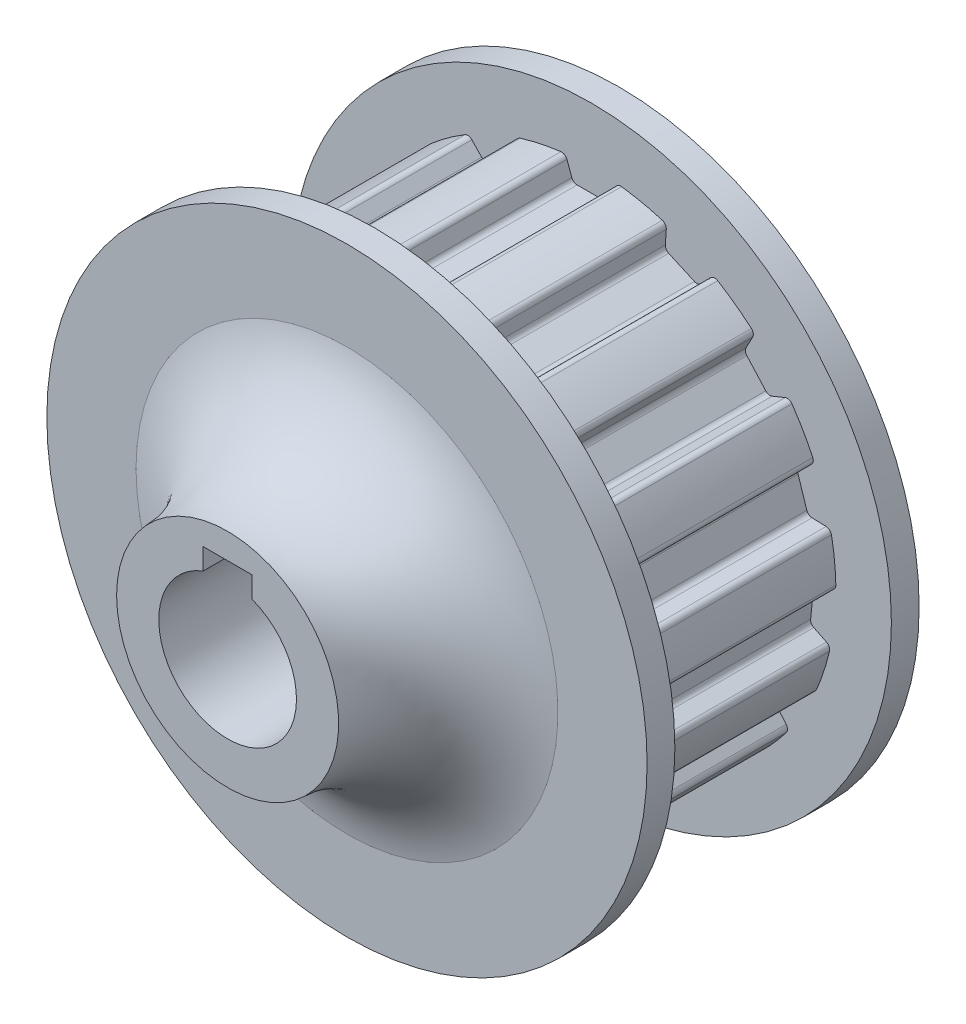
SolidWorks part; units mm, degrees
ref_plane "Front Plane" through (0, 0, 0) normal (0, 0, 1) x (1, 0, 0)
ref_plane "Top Plane" through (0, 0, 0) normal (0, 1, 0) x (1, 0, 0)
ref_plane "Right Plane" through (0, 0, 0) normal (1, 0, 0) x (0, 0, -1)
sketch "Sketch1" plane through (0, 0, 0) normal (0, 1, 0) x (1, 0, 0)
  line L0 (0, 36.1296) -> (0, -19.4741) construction
sketch "Sketch7" plane through (0, 0, 0) normal (0, 0, 1) x (1, 0, 0)
  line L0 (0, 0) -> (0, 20.9536) construction
  line L1 (-2.325, 21.9086) -> (-2.9401, 23.5986) construction
  line L2 (-2.325, 21.9086) -> (-1.6298, 19.9986) construction
  line L3 (-1.6298, 19.9986) -> (1.6298, 19.9986) construction
  line L4 (1.6298, 19.9986) -> (2.325, 21.9086) construction
  line L5 (2.325, 21.9086) -> (-2.325, 21.9086) construction
  line L6 (0, 19.9986) -> (0, 21.9086) construction
  line L7 (2.325, 21.9086) -> (2.9401, 23.5986) construction
  line L8 (-2.9401, 23.5986) -> (2.9401, 23.5986) construction
  line L9 (0, 0) -> (8.5226, 19.1421) construction
  line L10 (8.5226, 19.1421) -> (8.9611, 20.1269) construction
  line L11 (0, 21.9086) -> (0, 22.0316) construction
  line L12 (0, 22.0316) -> (0, 23.7811) construction
  line L13 (0, 22.9064) -> (9.3169, 20.926) construction
  line L14 (8.9611, 20.1269) -> (9.6726, 21.7251) construction
  circle A1 centre (0, 0) radius 20.9536 construction
  circle A2 centre (-1.2727, 20.5086) radius 0.51 construction
  circle A3 centre (1.2727, 20.5086) radius 0.51 construction
  circle A4 centre (0, 0) radius 22.0316
  circle A5 centre (0, 0) radius 23.7811 construction
  dimension "D3" = 40
  dimension "D6" = 1.02
  dimension "D1" = 3.6
  dimension "D2" = 24
  dimension "D7" = 9.525
  dimension "D4" = 1.91
  dimension "D5" = 4.65
extrude "Boss-Extrude1" add sketch "Sketch7" along normal blind 7.25 and the other way blind 7.25 contours A4 region at (0, 0, 0)
sketch "Sketch14" plane through (0, 0, 0) normal (1, 0, 0) x (0, 0, -1)
  line L0 (-18, 0) -> (-18, 10)
  line L1 (-18, 0) -> (0, 0)
  line L2 (0, 0) -> (0, 19)
  line L3 (0, 19) -> (-7.25, 19)
  line L4 (-7.25, 19) -> (-18, 10)
  line L5 (-7.25, 22.0316) -> (-7.25, -22.0316) construction
  line L6 (-18, 6.7395) -> (-3.3555, 19) construction
  arc A0 (-7.25, 19) -> (-18, 10) centre (-18.1316, 21.0773) cw
  dimension "D1" = 10
  dimension "D2" = 19
  dimension "D3" = 18
  dimension "D4" = 2.5
revolve "Revolve1" add sketch "Sketch14" angle 360 about L0 region at (0, 7.5733, 7.5341) region at (0, 9.2725, 16.1663) region at (0, 17.2765, 6.6188)
sketch "Sketch9" plane through (0, 0, 0) normal (0, 0, 1) x (1, 0, 0)
  line L0 (2, 0) -> (-2, 0) construction
  line L1 (-2, 0) -> (-2, 7.5) construction
  line L2 (-2, 7.5) -> (2, 7.5) construction
  line L3 (2, 7.5) -> (2, 0) construction
  circle A0 centre (0, 0) radius 6 construction
  dimension "D1" = 12
  dimension "D2" = 4
  dimension "D3" = 7.5
sketch "Sketch10" plane through (0, 0, 0) normal (0, 0, 1) x (1, 0, 0)
  line L0 (2, 0) -> (-2, 0) construction
  line L1 (-2.2, 7.7) -> (2.2, 7.7)
  line L2 (-2.2, 7.7) -> (-2.2, 0)
  line L3 (-2.2, 0) -> (2.2, 0)
  line L4 (2.2, 7.7) -> (2.2, 0)
  line L5 (-2, 7.5) -> (2, 7.5) construction
  line L6 (2, 7.5) -> (2, 0) construction
  circle A0 centre (0, 0) radius 6.2
  circle A1 centre (0, 0) radius 6 construction
  dimension "D1" = 0.2
  dimension "D2" = 0.2
  dimension "D3" = 0.2
extrude "Cut-Extrude3" cut sketch "Sketch10" against normal through all both and the other way through all contours A0 L4 L1 L2 | L2 A0 L4 L3 | L4 A0 L2 L3 region at (0, 6.8793, 0) region at (0, 3.0348, 0) region at (0, -0.8613, 0)
sketch "Sketch11" plane through (0, 0, 0) normal (0, 1, 0) x (1, 0, 0)
  line L0 (22.0316, 7.25) -> (-22.0316, 7.25) construction
  line L1 (11, 7.25) -> (17.5, 7.25)
  line L2 (11, 7.25) -> (11, 4.75)
  line L3 (11, 4.75) -> (17.5, 4.75)
  line L4 (17.5, 7.25) -> (17.5, 4.75)
  line L5 (-22.0316, -7.25) -> (22.0316, -7.25) construction
  line L6 (11, -7.25) -> (17.5, -7.25)
  line L7 (11, -7.25) -> (11, -4.75)
  line L8 (11, -4.75) -> (17.5, -4.75)
  line L9 (17.5, -7.25) -> (17.5, -4.75)
  line L11 (11, 4.75) -> (11, -4.75) construction
  line L12 (17.5, -4.75) -> (17.5, 4.75) construction
  line L13 (6.2, 7.25) -> (-6.2, 7.25) construction
  line L14 (0, 7.25) -> (22.5, 7.25)
  line L15 (0, 7.25) -> (0, -7.25)
  line L16 (0, -7.25) -> (22.5, -7.25)
  line L17 (22.5, 7.25) -> (22.5, -7.25)
  line L18 (-6.2, -7.25) -> (6.2, -7.25) construction
  line L19 (6, 7.25) -> (6, -7.25) construction
  dimension "D1" = 22.5
  dimension "D2" = 6
  dimension "D3" = 5
  dimension "D4" = 5
  dimension "D5" = 2.5
revolve "Cut-Revolve1" [suppressed] cut sketch "Sketch11" angle 360 about L0
sketch "Sketch15" plane through (0, 0, -7.25) normal (0, 0, -1) x (-1, 0, 0)
  circle A0 centre (0, 0) radius 8.0081
  circle A1 centre (0, 0) radius 2.25
  dimension "D1" = 4.5
extrude "Boss-Extrude2" add sketch "Sketch15" against normal blind 5.5
sketch "Sketch16" plane through (0, 0, -7.25) normal (0, 0, -1) x (-1, 0, 0)
  circle A0 centre (0, 0) radius 5
  dimension "D1" = 10
extrude "Cut-Extrude4" cut sketch "Sketch16" against normal blind 3
sketch "Sketch17" plane through (0, 0, -7.25) normal (0, 0, -1) x (-1, 0, 0)
  circle A0 centre (0, 0) radius 22.0316
  circle A1 centre (0, 0) radius 22.0316 construction
  circle A2 centre (0, 0) radius 5
  circle A3 centre (0, 0) radius 5 construction
extrude "Boss-Extrude3" add sketch "Sketch17" along normal blind 7.5
sketch "Sketch8" plane through (0, 0, 0) normal (0, 0, 1) x (1, 0, 0)
  line L6 (-1.6298, 19.9986) -> (-2.3698, 22.0316)
  line L7 (-2.3698, 22.0316) -> (2.3698, 22.0316)
  line L8 (2.3698, 22.0316) -> (1.6298, 19.9986)
  line L9 (1.6298, 19.9986) -> (-1.6298, 19.9986)
  line L10 (-2.325, 21.9086) -> (-1.6298, 19.9986) construction
  line L11 (1.6298, 19.9986) -> (2.325, 21.9086) construction
  line L12 (6.6453, 18.9326) -> (6.7962, 21.0908)
  line L13 (6.7962, 21.0908) -> (11.126, 19.163)
  line L14 (11.126, 19.163) -> (9.6231, 17.6067)
  line L15 (9.6231, 17.6067) -> (6.6453, 18.9326)
  line L16 (13.7713, 14.5929) -> (14.787, 16.5031)
  line L17 (14.787, 16.5031) -> (17.9584, 12.981)
  line L18 (17.9584, 12.981) -> (15.9524, 12.1705)
  line L19 (15.9524, 12.1705) -> (13.7713, 14.5929)
  line L20 (18.5162, 7.73) -> (20.221, 9.0619)
  line L21 (20.221, 9.0619) -> (21.6856, 4.5544)
  line L22 (21.6856, 4.5544) -> (19.5235, 4.6299)
  line L23 (19.5235, 4.6299) -> (18.5162, 7.73)
  line L24 (20.0594, -0.4695) -> (22.1587, 0.0539)
  line L25 (22.1587, 0.0539) -> (21.6632, -4.6597)
  line L26 (21.6632, -4.6597) -> (19.7187, -3.7113)
  line L27 (19.7187, -3.7113) -> (20.0594, -0.4695)
  line L28 (18.1342, -8.5879) -> (20.2649, -8.9635)
  line L29 (20.2649, -8.9635) -> (17.8951, -13.0681)
  line L30 (17.8951, -13.0681) -> (16.5044, -11.4108)
  line L31 (16.5044, -11.4108) -> (18.1342, -8.5879)
  line L32 (13.0734, -15.2212) -> (14.8671, -16.4311)
  line L33 (14.8671, -16.4311) -> (11.0327, -19.2169)
  line L34 (11.0327, -19.2169) -> (10.4363, -17.1372)
  line L35 (10.4363, -17.1372) -> (13.0734, -15.2212)
  line L36 (5.7521, -19.2227) -> (6.8986, -21.0575)
  line L37 (6.8986, -21.0575) -> (2.2626, -22.0429)
  line L38 (2.2626, -22.0429) -> (2.5637, -19.9005)
  line L39 (2.5637, -19.9005) -> (5.7521, -19.2227)
  line L40 (-2.5637, -19.9005) -> (-2.2626, -22.0429)
  line L41 (-2.2626, -22.0429) -> (-6.8986, -21.0575)
  line L42 (-6.8986, -21.0575) -> (-5.7521, -19.2227)
  line L43 (-5.7521, -19.2227) -> (-2.5637, -19.9005)
  line L44 (-10.4363, -17.1372) -> (-11.0327, -19.2169)
  line L45 (-11.0327, -19.2169) -> (-14.8671, -16.4311)
  line L46 (-14.8671, -16.4311) -> (-13.0734, -15.2212)
  line L47 (-13.0734, -15.2212) -> (-10.4363, -17.1372)
  line L48 (-16.5044, -11.4108) -> (-17.8951, -13.0681)
  line L49 (-17.8951, -13.0681) -> (-20.2649, -8.9635)
  line L50 (-20.2649, -8.9635) -> (-18.1342, -8.5879)
  line L51 (-18.1342, -8.5879) -> (-16.5044, -11.4108)
  line L52 (-19.7187, -3.7113) -> (-21.6632, -4.6597)
  line L53 (-21.6632, -4.6597) -> (-22.1587, 0.0539)
  line L54 (-22.1587, 0.0539) -> (-20.0594, -0.4695)
  line L55 (-20.0594, -0.4695) -> (-19.7187, -3.7113)
  line L56 (-19.5235, 4.6299) -> (-21.6856, 4.5544)
  line L57 (-21.6856, 4.5544) -> (-20.221, 9.0619)
  line L58 (-20.221, 9.0619) -> (-18.5162, 7.73)
  line L59 (-18.5162, 7.73) -> (-19.5235, 4.6299)
  line L60 (-15.9524, 12.1705) -> (-17.9584, 12.981)
  line L61 (-17.9584, 12.981) -> (-14.787, 16.5031)
  line L62 (-14.787, 16.5031) -> (-13.7713, 14.5929)
  line L63 (-13.7713, 14.5929) -> (-15.9524, 12.1705)
  line L64 (-9.6231, 17.6067) -> (-11.126, 19.163)
  line L65 (-11.126, 19.163) -> (-6.7962, 21.0908)
  line L66 (-6.7962, 21.0908) -> (-6.6453, 18.9326)
  line L67 (-6.6453, 18.9326) -> (-9.6231, 17.6067)
  circle A0 centre (0, 0) radius 22.0316 construction
  point P119 (0, 0)
  dimension "D1" = 15
extrude "Cut-Extrude2" cut sketch "Sketch8" against normal through all both and the other way through all
fillet "Fillet2" radius 0.51 60 edges at (-6.787, 20.9602, -3.75) (-11.035, 19.0689, -3.75) (-14.7256, 16.3875, -3.75) (-17.837, 12.9319, -3.75) (-20.1179, 8.9813, -3.75) (-21.5548, 4.5589, -3.75) (-22.0316, 0.0222, -3.75) (-21.5456, -4.6023, -3.75) (-20.1359, -8.9408, -3.75) (-17.8109, -12.9678, -3.75) (-14.7585, -16.3578, -3.75) (-10.9966, -19.0911, -3.75) (-6.8293, -20.9465, -3.75) (-2.2809, -21.9133, -3.75) (2.2809, -21.9133, -3.75) (6.8293, -20.9465, -3.75) (10.9966, -19.0911, -3.75) (14.7585, -16.3578, -3.75) (17.8109, -12.9678, -3.75) (20.1359, -8.9408, -3.75) (21.5456, -4.6023, -3.75) (22.0316, 0.0222, -3.75) (21.5548, 4.5589, -3.75) (20.1179, 8.9813, -3.75) (17.837, 12.9319, -3.75) (14.7256, 16.3875, -3.75) (11.035, 19.0689, -3.75) (6.787, 20.9602, -3.75) (2.325, 21.9086, -3.75) (-6.6453, 18.9326, -3.75) (-9.6231, 17.6067, -3.75) (-13.7713, 14.5929, -3.75) (-15.9524, 12.1705, -3.75) (-18.5162, 7.73, -3.75) (-19.5235, 4.6299, -3.75) (-20.0594, -0.4695, -3.75) (-19.7187, -3.7113, -3.75) (-18.1342, -8.5879, -3.75) (-16.5044, -11.4108, -3.75) (-13.0734, -15.2212, -3.75) (-10.4363, -17.1372, -3.75) (-5.7521, -19.2227, -3.75) (-2.5637, -19.9005, -3.75) (2.5637, -19.9005, -3.75) (5.7521, -19.2227, -3.75) (10.4363, -17.1372, -3.75) (13.0734, -15.2212, -3.75) (16.5044, -11.4108, -3.75) (18.1342, -8.5879, -3.75) (19.7187, -3.7113, -3.75) (20.0594, -0.4695, -3.75) (19.5235, 4.6299, -3.75) (18.5162, 7.73, -3.75) (15.9524, 12.1705, -3.75) (13.7713, 14.5929, -3.75) (9.6231, 17.6067, -3.75) (6.6453, 18.9326, -3.75) (1.6298, 19.9986, -3.75) (-1.6298, 19.9986, -3.75) (-2.325, 21.9086, -3.75)
sketch "Sketch18" plane through (0, 0, -14.75) normal (0, 0, -1) x (-1, 0, 0)
  circle A0 centre (0, 0) radius 5
  circle A1 centre (0, 0) radius 27.0316
  circle A2 centre (0, 0) radius 22.0316
  circle A3 centre (0, 0) radius 5 construction
  arc A4 (-2.7297, 21.8619) -> (-6.3983, 21.0821) centre (0, 0) ccw construction
  dimension "D1" = 5
extrude "Boss-Extrude4" add sketch "Sketch18" along normal blind 2.5 contours A1 A2 | A2 A0 region at (26.2671, 0, -14.75) region at (21.4085, 0, -14.75)
sketch "Sketch19" plane through (0, 0, 7.25) normal (0, 0, 1) x (1, 0, 0)
  circle A0 centre (0, 0) radius 19
  circle A1 centre (0, 0) radius 27.0316
  circle A2 centre (0, 0) radius 27.0316 construction
  circle A3 centre (0, 0) radius 19 construction
extrude "Boss-Extrude5" add sketch "Sketch19" against normal blind 2.5
fillet "Fillet3" [suppressed] radius 0.5
sketch "Sketch20" plane through (0, 0, 18) normal (0, 0, 1) x (1, 0, 0)
  line L0 (-2.2, 5.7966) -> (-2.2, 7.7)
  line L1 (-2.2, 7.7) -> (2.2, 7.7)
  line L2 (-2.2, 7.7) -> (2.2, 7.7) construction
  line L3 (2.2, 7.7) -> (2.2, 5.7966)
  circle A0 centre (0, 0) radius 6.2
  arc A1 (-2.2, 5.7966) -> (2.2, 5.7966) centre (0, 0) ccw construction
  arc M2 (2.2, 5.7966) -> (-2.2, 5.7966) centre (0, 0) cw
  line M3 (-2.2, 5.7966) -> (-2.2, 7.7)
  line M4 (-2.2, 7.7) -> (2.2, 7.7)
  line M5 (2.2, 7.7) -> (2.2, 5.7966)
extrude "Cut-Extrude5" cut sketch "Sketch20" against normal through all contours A0 M5 M4 M3 | A0 M2 region at (0, 6.8793, 18) region at (0, 0, 18)
ref_plane "Plane1" through (0, 0, -5.25) normal (0, 0, 1) x (1, 0, 0)
sketch "Sketch21" plane through (0, 0, -5.25) normal (0, 0, 1) x (1, 0, 0)
  circle A0 centre (0, 0) radius 8.0081
  circle A1 centre (0, 0) radius 2.25
  circle A2 centre (0, 0) radius 6.2
  arc A3 (-2.2, 5.7966) -> (2.2, 5.7966) centre (0, 0) ccw construction
  dimension "D1" = 4.5
extrude "Boss-Extrude6" add sketch "Sketch21" against normal blind 2.5 contours A2 A1 | A0 A2 region at (-7.7816, 0, -5.25) region at (-6.0246, 0, -5.25)
extrude "Boss-Extrude7" add sketch "Sketch21<4>" against normal up to surface (12 mm away) contours A0 A2 region at (-7.7816, 0, -5.25) up to face at (0, 3.7491, -17.25)
sketch "Sketch21<4>" plane through (0, 0, -5.25) normal (0, 0, 1) x (1, 0, 0) same geometry as "Sketch21"
